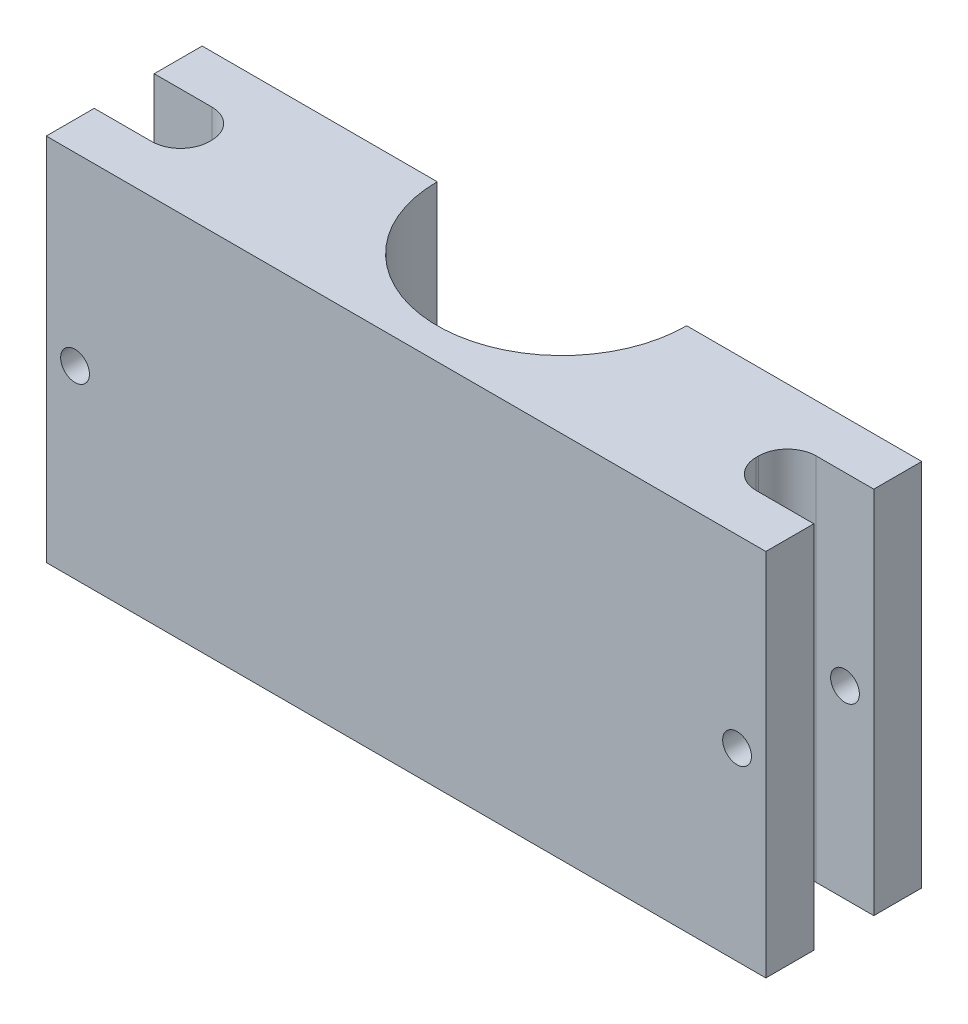
SolidWorks part; units mm, degrees
ref_plane "Front Plane" through (0, 0, 0) normal (0, 0, 1) x (1, 0, 0)
ref_plane "Top Plane" through (0, 0, 0) normal (0, 1, 0) x (1, 0, 0)
ref_plane "Right Plane" through (0, 0, 0) normal (1, 0, 0) x (0, 0, -1)
sketch "Sketch1" plane through (0, 0, 0) normal (0, 1, 0) x (1, 0, 0)
  line L0 (-26, 0) -> (26, 0)
  line L1 (-26, 0) -> (-75, 0)
  line L2 (-75, 0) -> (-75, -10)
  line L3 (-75, -10) -> (-63, -10)
  line L4 (-57, -16) -> (-57, -16.5)
  line L5 (-63, -22.5) -> (-75, -22.5)
  line L6 (-75, -22.5) -> (-75, -32.5)
  line L7 (-75, -32.5) -> (75, -32.5)
  line L8 (0, -32.5) -> (0, -26) construction
  line L9 (75, -22.5) -> (75, -32.5)
  line L10 (63, -22.5) -> (75, -22.5)
  line L11 (57, -16) -> (57, -16.5)
  line L12 (75, -10) -> (63, -10)
  line L13 (75, 0) -> (75, -10)
  line L14 (26, 0) -> (75, 0)
  line L15 (-50, 0) -> (-50, -32.5) construction
  arc A0 (-26, 0) -> (26, 0) centre (0, 0) ccw
  arc A1 (-57, -16.5) -> (-63, -22.5) centre (-63, -16.5) cw
  arc A2 (-63, -10) -> (-57, -16) centre (-63, -16) cw
  arc A3 (57, -16.5) -> (63, -22.5) centre (63, -16.5) ccw
  arc A4 (63, -10) -> (57, -16) centre (63, -16) ccw
  point P32 (-57, -22.5)
  point P35 (-57, -10)
  dimension "D1" = 6.5
  dimension "D2" = 26
  dimension "D4" = 6
  dimension "D8" = 50
  dimension "D3" = 18
  dimension "D5" = 10
  dimension "D6" = 10
  dimension "D7" = 25
extrude "Boss-Extrude1" add sketch "Sketch1" along normal blind 38.5 and the other way blind 38.5 contours L7 L8 A0 L1 L2 L3 L4 L5 L6 | L8 L7 L9 L10 L11 L12 L13 L14 A0 region at (-42.191, 0, 17.8816) region at (42.191, 0, 17.8816)
sketch "Sketch5" plane through (0, 0, 32.5) normal (0, 0, 1) x (1, 0, 0)
  line L0 (0, 0) -> (0, 38.5) construction
  line L1 (-75, 38.5) -> (75, 38.5) construction
  line L3 (-63, 38.5) -> (-75, 38.5) construction
  line L4 (-63, 38.5) -> (-75, 38.5)
  line L5 (-63, -38.5) -> (-63, 38.5) construction
  line L6 (-63, -38.5) -> (-63, 38.5)
  line L7 (-69, 0) -> (-75, 0) construction
  line L8 (-75, -38.5) -> (-75, 38.5) construction
  line L9 (-63, 0) -> (-69, 0) construction
  circle A0 centre (-69, 0) radius 3
  circle A2 centre (69, 0) radius 3
  point P10 (0, 0)
  point P17 (0, 0)
  point P18 (-65, 0)
  point P19 (-77, 0)
  dimension "D1" = 6
extrude "Cut-Extrude1" cut sketch "Sketch5" against normal through all contours A0 | A2 region at (-69, 0, 32.5) region at (69, 0, 32.5)
